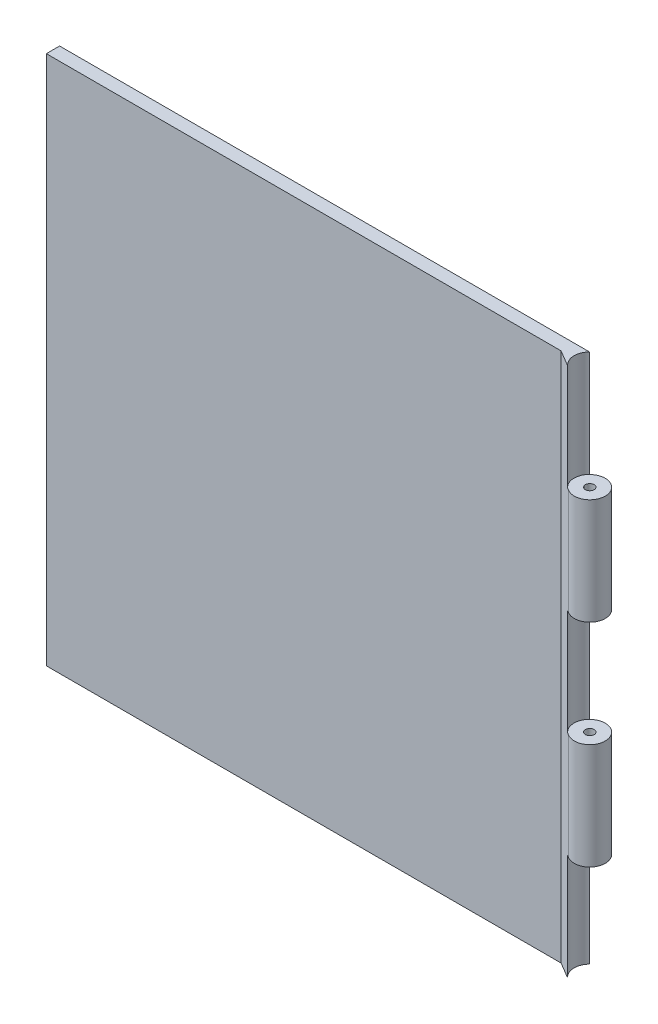
SolidWorks part; units mm, degrees
ref_plane "Plano frontal" through (0, 0, 0) normal (0, 0, 1) x (1, 0, 0)
ref_plane "Plano superior" through (0, 0, 0) normal (0, 1, 0) x (1, 0, 0)
ref_plane "Plano direito" through (0, 0, 0) normal (1, 0, 0) x (0, 0, -1)
sketch "Esboço1" plane through (0, 0, 0) normal (0, 0, 1) x (1, 0, 0)
  line L1 (-60, -60) -> (60, -60)
  line L2 (-60, -60) -> (-60, 60)
  line L3 (-60, 60) -> (60, 60)
  line L4 (60, -60) -> (60, 60)
  line L5 (-60, -60) -> (60, 60) construction
  line L6 (-60, 60) -> (60, -60) construction
  point P0 (0, 0)
  dimension "D1" = 120
  dimension "D2" = 120
extrude "Ressalto-extrusão1" add sketch "Esboço1" along normal blind 3
sketch "Esboço2" plane through (0, 0, 0) normal (0, 0, -1) x (-1, 0, 0)
  line L8 (-56.4, 56.4) -> (-56.4, -56.4)
  line L9 (-56.4, -56.4) -> (56.4, -56.4)
  line L10 (56.4, -56.4) -> (56.4, 56.4)
  line L11 (56.4, 56.4) -> (-56.4, 56.4)
  line L12 (-56.4, 56.4) -> (-56.4, -56.4)
  line L13 (-56.4, -56.4) -> (56.4, -56.4)
  line L14 (56.4, -56.4) -> (56.4, 56.4)
  line L15 (56.4, 56.4) -> (-56.4, 56.4)
  dimension "D1" = 3.6
extrude "Ressalto-extrusão2" add sketch "Esboço2" along normal blind 2
sketch "Esboço3" plane through (0, 0, -2) normal (0, 0, -1) x (-1, 0, 0)
  line L8 (54.4, 54.4) -> (-54.4, 54.4)
  line L9 (-54.4, 54.4) -> (-54.4, -54.4)
  line L10 (-54.4, -54.4) -> (54.4, -54.4)
  line L11 (54.4, -54.4) -> (54.4, 54.4)
  line L12 (54.4, 54.4) -> (-54.4, 54.4)
  line L13 (-54.4, 54.4) -> (-54.4, -54.4)
  line L14 (-54.4, -54.4) -> (54.4, -54.4)
  line L15 (54.4, -54.4) -> (54.4, 54.4)
  dimension "D1" = 2
extrude "Corte-extrusão1" cut sketch "Esboço3" against normal blind 2
chamfer "Chanfro1" distance 0.5 angle 45 4 edges at (-56.4, 0, -2) (0, -56.4, -2) (56.4, 0, -2) (0, 56.4, -2)
sketch "Esboço5" plane through (0, 0, 0) normal (0, 1, 0) x (1, 0, 0)
  line L0 (48.3486, 0) -> (60, 0) construction
  line L1 (60, 0) -> (60, 10.0434) construction
  line L2 (60, 10.0434) -> (48.3486, 10.0434) construction
  line L3 (48.3486, 10.0434) -> (48.3486, 0) construction
  line L4 (60, -3) -> (60, 0) construction
  line L5 (62.4749, -2.4749) -> (65.9749, -2.4749) construction
  line L6 (62.4749, -2.4749) -> (60, 0) construction
  line L7 (60.6913, -5.4863) -> (56.4933, -3)
  line L8 (60, -3) -> (-60, -3) construction
  line L9 (56.4933, -3) -> (59.0145, -3)
  arc A0 (60.6913, -5.4863) -> (59.0145, -3) centre (62.4749, -2.4749) ccw
  dimension "D1" = 135
  dimension "D2" = 3.5
extrude "Ressalto-extrusão3" add sketch "Esboço5" along normal mid plane 120
sketch "Esboço6" plane through (0, 60, 0) normal (0, 1, 0) x (1, 0, 0)
  circle A0 centre (62.4749, -2.4749) radius 3.55
  dimension "D1" = 7.1
extrude "Corte-extrusão2" cut sketch "Esboço6" against normal blind 24
ref_plane "Plano1" through (0, 12, 0) normal (0, 1, 0) x (1, 0, 0)
sketch "Esboço7" plane through (0, 12, 0) normal (0, 1, 0) x (1, 0, 0)
  circle A0 centre (62.4749, -2.4749) radius 3.55
extrude "Corte-extrusão3" cut sketch "Esboço7" against normal blind 24
ref_plane "Plano2" through (0, -36, 0) normal (0, 1, 0) x (1, 0, 0)
sketch "Esboço9" plane through (0, -36, 0) normal (0, 1, 0) x (1, 0, 0)
  circle A0 centre (62.4749, -2.4749) radius 3.55
extrude "Corte-extrusão4" cut sketch "Esboço9" against normal blind 24
sketch "Esboço10" plane through (0, 60, 0) normal (0, 1, 0) x (1, 0, 0)
  circle A0 centre (62.4749, -2.4749) radius 1
extrude "Corte-extrusão5" cut sketch "Esboço10" against normal through all both and the other way through all
ref_plane "Plano3" through (0, 12, 0) normal (0, 1, 0) x (1, 0, 0)
sketch "Esboço11" plane through (0, 12, 0) normal (0, 1, 0) x (1, 0, 0)
  line L0 (-60.6256, -2.4492) -> (-57.2551, 0.3085)
  line L1 (-57.2551, 0.3085) -> (-60.6256, 0.3085)
  line L2 (-60.6256, 0.3085) -> (-60.6256, -2.4492)
extrude "Corte-extrusão6" cut sketch "Esboço11" against normal blind 24
sketch "Esboço14" plane through (0, 0, 0) normal (0, 0, -1) x (-1, 0, 0)
  line L0 (54.4, -54.4) -> (54.4, 54.4) construction
  line L1 (49.4, 5) -> (54.4, 5)
  line L2 (54.4, -54.4) -> (54.4, 54.4) construction
  line L3 (54.4, 5) -> (54.4, -5)
  line L4 (54.4, -5) -> (49.4, -5)
  arc A0 (49.4, 5) -> (49.4, -5) centre (49.4, 0) ccw
  dimension "D1" = 10
extrude "Ressalto-extrusão13" add sketch "Esboço14" along normal blind 3
fillet "Filete1" radius 3 3 edges at (-51.9, 5, 0) (-51.9, -5, 0) (-44.4, 0, 0)
